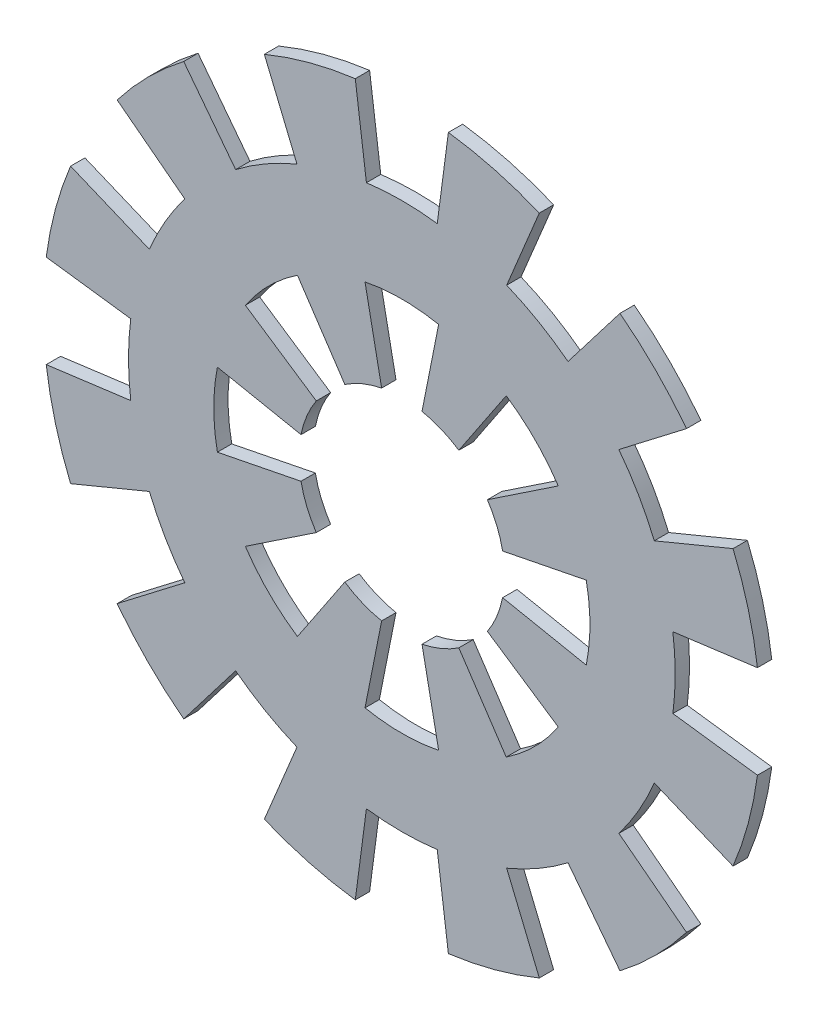
SolidWorks part; units mm, degrees
ref_plane "Front Plane" through (0, 0, 0) normal (0, 0, 1) x (1, 0, 0)
ref_plane "Top Plane" through (0, 0, 0) normal (0, 1, 0) x (1, 0, 0)
ref_plane "Right Plane" through (0, 0, 0) normal (1, 0, 0) x (0, 0, -1)
sketch "BodySke" plane through (0, 0, 0) normal (0, 1, 0) x (1, 0, 0)
  line L0 (0, 0) -> (0, 8) construction
  line L1 (0, 0) -> (-12, 0) construction
  line L2 (2.15, 0) -> (7.5, 0)
  line L3 (2.15, 0) -> (2.15, 0.3)
  line L4 (2.15, 0.3) -> (7.5, 0.3)
  line L5 (7.5, 0) -> (7.5, 0.3)
revolve "BaseBody" add sketch "BodySke" angle 360 about L0
sketch "ToothInSke" plane through (0, 0, 0) normal (0, 0, 1) x (1, 0, 0)
  line L0 (0, 0) -> (0, 2.7341) construction
  line L2 (-0.7701, 3.8572) -> (-0.4222, 2.1081)
  line L3 (-0.4222, 2.1081) -> (0.4222, 2.1081)
  line L4 (0.7701, 3.8572) -> (0.4222, 2.1081)
  arc A0 (0.7701, 3.8572) -> (-0.7701, 3.8572) centre (0, 0) ccw construction
  arc A1 (-3.9333, 0) -> (3.9333, 0) centre (0, 0) ccw construction
  circle A2 centre (0, 0) radius 2.15 construction
  circle A3 centre (0, 0) radius 2.15 construction
  arc A4 (0.7701, 3.8572) -> (-0.7701, 3.8572) centre (0, 0) ccw
  point P11 (0, 2.1081)
  point P12 (0, 3.9333)
  dimension "D1" = 7.8667
  dimension "D2" = 0.8443
  dimension "D3" = 22.5
extrude "ToothCutIn" cut sketch "ToothInSke" against normal through all
pattern_circular "ToothInPat" count 8 over 360 about axis through (0, 0, 0) along (0, 0, -1) of "ToothCutIn"
sketch "ToothExSke" plane through (0, 0, 0) normal (0, 0, 1) x (1, 0, 0)
  line L0 (0, 0) -> (8.6397, 0) construction
  line L1 (7.5, -0.9817) -> (7.5, 0.9817)
  line L2 (7.5, 0.9817) -> (5.6685, 0.7406)
  line L3 (7.5, -0.9817) -> (5.6685, -0.7406)
  arc A0 (-5.7167, 0) -> (5.6685, 0.7406) centre (0, 0) ccw construction
  circle A1 centre (0, 0) radius 7.5 construction
  circle A2 centre (0, 0) radius 7.5 construction
  arc A3 (5.6685, -0.7406) -> (5.6685, 0.7406) centre (0, 0) ccw
  point P11 (7.5, 0)
  dimension "D1" = 11.4333
  dimension "D2" = 1.9635
  dimension "D3" = 15
extrude "ToothCutEx" cut sketch "ToothExSke" against normal through all
pattern_circular "ToothExPat" count 12 over 360 about axis through (0, 0, 0) along (0, 0, -1) of "ToothCutEx"
equation "\"D1@ToothInSke\" =  \"Inner_dia@BodySke\" +  ( \"Outer_dia@BodySke\" - \"Inner_dia@BodySke\" )  / 3"
equation "\"D2@ToothInSke\" =  pi  * \"Inner_dia@BodySke\" / 2 / \"Num_inpat@BodySke\""
equation "\"D3@ToothInSke\" = 180 / \"Num_inpat@BodySke\""
equation "\"Num_inpat@ToothInPat\" = \"Num_inpat@BodySke\""
equation "\"D1@ToothExSke\" = \"Inner_dia@BodySke\" +  ( \"Outer_dia@BodySke\" - \"Inner_dia@BodySke\" )  * 2 / 3"
equation "\"D2@ToothExSke\" = pi  * \"Outer_dia@BodySke\" / 2 / \"Num_expat@BodySke\""
equation "\"D3@ToothExSke\" = 180 / \"Num_expat@BodySke\""
equation "\"Num_expat@ToothExPat\" = \"Num_expat@BodySke\""
